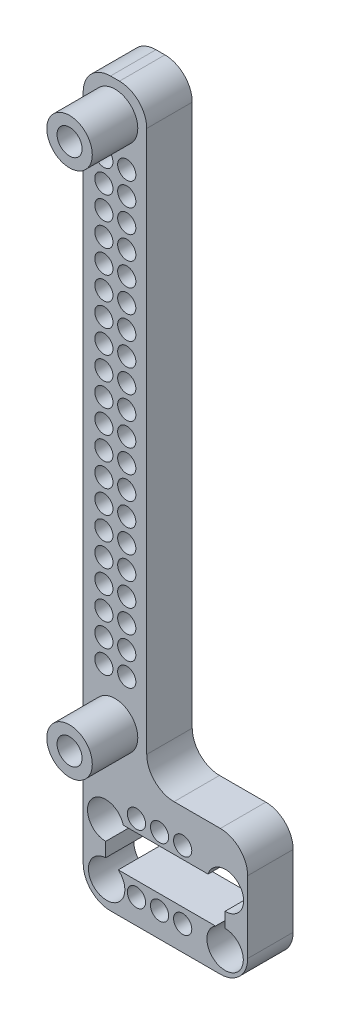
SolidWorks part; units mm, degrees
ref_plane "Front Plane" through (0, 0, 0) normal (0, 0, 1) x (1, 0, 0)
ref_plane "Top Plane" through (0, 0, 0) normal (0, 1, 0) x (1, 0, 0)
ref_plane "Right Plane" through (0, 0, 0) normal (1, 0, 0) x (0, 0, -1)
sketch "Sketch2" plane through (0, 0, 0) normal (0, 0, 1) x (1, 0, 0)
  line L1 (134.0969, -34.7678) -> (141.0811, -34.7678)
  line L2 (134.0969, -34.7678) -> (134.0969, -102.772)
  line L3 (134.0969, -102.772) -> (141.0811, -102.772)
  line L4 (141.0811, -34.7678) -> (141.0811, -102.772)
  line L5 (134.0969, -34.7678) -> (141.0811, -102.772) construction
  line L6 (134.0969, -102.772) -> (141.0811, -34.7678) construction
  line L7 (134.0969, -100.3445) -> (152.1718, -100.3445)
  line L8 (134.0969, -100.3445) -> (134.0969, -114.2263)
  line L9 (134.0969, -114.2263) -> (152.1718, -114.2263)
  line L10 (152.1718, -100.3445) -> (152.1718, -114.2263)
  line L11 (134.0969, -100.3445) -> (152.1718, -114.2263) construction
  line L12 (134.0969, -114.2263) -> (152.1718, -100.3445) construction
  line L13 (136.5675, -105.3676) -> (149.6921, -105.3676)
  line L14 (136.5675, -105.3676) -> (136.5675, -109.8964)
  line L15 (136.5675, -109.8964) -> (149.6921, -109.8964)
  line L16 (149.6921, -105.3676) -> (149.6921, -109.8964)
  line L17 (136.5675, -105.3676) -> (149.6921, -109.8964) construction
  line L18 (136.5675, -109.8964) -> (149.6921, -105.3676) construction
  circle A0 centre (137.5969, -96.2678) radius 1.375
  circle A1 centre (137.5969, -38.2678) radius 1.375
  circle A3 centre (138.8831, -42.7888) radius 1
  circle A4 centre (138.8831, -45.3288) radius 1
  circle A5 centre (138.8831, -47.8688) radius 1
  circle A6 centre (138.8831, -50.4088) radius 1
  circle A7 centre (138.8831, -52.9488) radius 1
  circle A8 centre (138.8831, -55.4888) radius 1
  circle A9 centre (138.8831, -58.0288) radius 1
  circle A10 centre (138.8831, -60.5688) radius 1
  circle A11 centre (138.8831, -63.1088) radius 1
  circle A12 centre (138.8831, -65.6488) radius 1
  circle A13 centre (138.8831, -68.1888) radius 1
  circle A14 centre (138.8831, -70.7288) radius 1
  circle A15 centre (138.8831, -73.2688) radius 1
  circle A16 centre (138.8831, -75.8088) radius 1
  circle A17 centre (138.8831, -78.3488) radius 1
  circle A18 centre (138.8831, -80.8888) radius 1
  circle A19 centre (138.8831, -83.4288) radius 1
  circle A20 centre (138.8831, -85.9688) radius 1
  circle A21 centre (138.8831, -88.5088) radius 1
  circle A22 centre (138.8831, -91.0488) radius 1
  circle A23 centre (136.3683, -42.829) radius 1
  circle A24 centre (137.5969, -38.2678) radius 2.5
  circle A25 centre (136.3683, -45.369) radius 1
  circle A26 centre (136.3683, -47.909) radius 1
  circle A27 centre (136.3683, -50.449) radius 1
  circle A28 centre (136.3683, -52.989) radius 1
  circle A29 centre (136.3683, -55.529) radius 1
  circle A30 centre (136.3683, -58.069) radius 1
  circle A31 centre (136.3683, -60.609) radius 1
  circle A32 centre (136.3683, -63.149) radius 1
  circle A33 centre (136.3683, -65.689) radius 1
  circle A34 centre (136.3683, -68.229) radius 1
  circle A35 centre (136.3683, -70.769) radius 1
  circle A36 centre (136.3683, -73.309) radius 1
  circle A37 centre (136.3683, -75.849) radius 1
  circle A38 centre (136.3683, -78.389) radius 1
  circle A39 centre (136.3683, -80.929) radius 1
  circle A40 centre (136.3683, -83.469) radius 1
  circle A41 centre (136.3683, -86.009) radius 1
  circle A42 centre (136.3683, -88.549) radius 1
  circle A43 centre (136.3683, -91.089) radius 1
  circle A44 centre (142.49, -104.0347) radius 1
  circle A45 centre (145.03, -104.0347) radius 1
  circle A46 centre (145.03, -111.4978) radius 1
  circle A47 centre (142.49, -111.4978) radius 1
  circle A48 centre (139.95, -111.4978) radius 1
  circle A49 centre (139.95, -104.0347) radius 1
  circle A50 centre (136.6728, -111.4348) radius 2
  circle A51 centre (136.5675, -105.8792) radius 1.9954
  circle A52 centre (149.6921, -111.5992) radius 2
  circle A53 centre (149.7274, -105.9664) radius 2
  circle A54 centre (146.769, -108.8935) radius 0.5
  circle A55 centre (146.769, -106.3535) radius 0.5
  circle A56 centre (144.229, -106.3535) radius 0.5
  circle A57 centre (144.229, -108.8935) radius 0.5
  circle A58 centre (141.689, -106.3535) radius 0.5
  circle A59 centre (141.689, -108.8935) radius 0.5
  circle A60 centre (139.149, -106.3535) radius 0.5
  circle A61 centre (139.149, -108.8935) radius 0.5
  circle A62 centre (137.5969, -96.2678) radius 2.5
  point P90 (143.1298, -107.632)
  point P104 (137.589, -68.7699)
  point P109 (143.1343, -107.2854)
  dimension "D1" = 20
  dimension "D2" = 20
extrude "Main Body" add sketch "Sketch2" along normal blind 5 contours L2 L7 L4 L1 A43 A42 A41 A40 A39 A38 A37 A36 A35 A34 A33 A32 A31 A30 A29 A28 A27 A26 A25 A23 A22 A21 A20 | L7 L2 L3 L4 | L10 L7 L4 L3 L8 L9 A61 A60 A59 A58 A57 A56 A55 A54 A53 A52 A51 A50 A49 A48 A47 A46 A45 A44 region at (137.5722, -67.8595, 0) region at (137.589, -101.5583, 0) region at (146.6264, -100.5724, 0)
fillet "Fillet1" radius 3 6 edges at (141.0811, -100.3445, 2.5) (152.1718, -100.3445, 2.5) (152.1718, -114.2263, 2.5) (134.0969, -114.2263, 2.5) (141.0811, -34.7678, 2.5) (134.0969, -34.7678, 2.5)
extrude "Straws" add sketch "Sketch2<3>" along normal blind 10 contours A24 A1 | A62 A0 region at (135.1676, -38.2678, 0) region at (135.1676, -96.2678, 0)
sketch "Sketch2<3>" plane through (0, 0, 0) normal (0, 0, 1) x (1, 0, 0) same geometry as "Sketch2"
